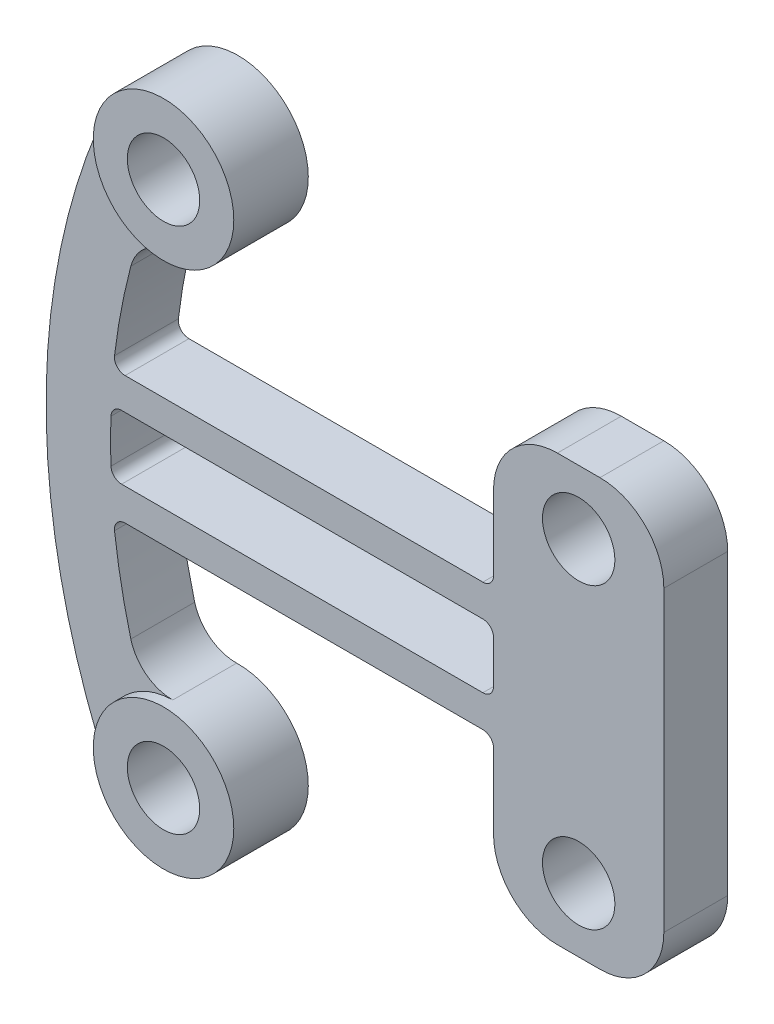
SolidWorks part; units mm, degrees
ref_plane "Front Plane" through (0, 0, 0) normal (0, 0, 1) x (1, 0, 0)
ref_plane "Top Plane" through (0, 0, 0) normal (0, 1, 0) x (1, 0, 0)
ref_plane "Right Plane" through (0, 0, 0) normal (1, 0, 0) x (0, 0, -1)
ref_plane "Plane1" through (0, 0, 0) normal (0, 0, -1) x (-1, 0, 0)
sketch "Sketch1" plane through (0, 0, 0) normal (0, 0, -1) x (-1, 0, 0)
  line L0 (-16, 3) -> (-16, -3)
  line L1 (-16, -3) -> (9.8641, -3)
  line L2 (9.8641, 3) -> (-16, 3)
  arc A0 (9.8641, -3) -> (8.4873, -9.4291) centre (-19.8438, 0) cw
  arc A1 (8.4873, -9.4291) -> (9.997, -13.7566) centre (7, -12.375) ccw
  arc A2 (9.997, -13.7566) -> (9.997, 13.7566) centre (-19.8438, 0) ccw
  arc A3 (9.997, 13.7566) -> (8.4873, 9.4291) centre (7, 12.375) ccw
  arc A4 (8.4873, 9.4291) -> (9.8641, 3) centre (-19.8438, 0) cw
extrude "Boss-Extrude1" add sketch "Sketch1" against normal blind 3
sketch "Sketch2" plane through (0, -3, 0) normal (0, -1, 0) x (1, 0, 0)
  line L0 (8, 3) -> (16, 3)
  line L1 (16, 3) -> (16, 0)
  line L2 (16, 0) -> (8, 0)
  line L3 (8, 0) -> (8, 3)
extrude "Boss-Extrude2" add sketch "Sketch2" along normal blind 7
sketch "Sketch3" plane through (0, 3, 0) normal (0, 1, 0) x (-1, 0, 0)
  line L0 (-16, 3) -> (-8, 3)
  line L1 (-8, 3) -> (-8, 0)
  line L2 (-8, 0) -> (-16, 0)
  line L3 (-16, 0) -> (-16, 3)
extrude "Boss-Extrude3" add sketch "Sketch3" along normal blind 7
sketch "Sketch4" plane through (0, 0, 3) normal (0, 0, 1) x (1, 0, 0)
  circle A0 centre (-7, 12.375) radius 3.3001
extrude "Boss-Extrude4" add sketch "Sketch4" along normal blind 0.5
sketch "Sketch5" plane through (0, 0, 3) normal (0, 0, 1) x (1, 0, 0)
  circle A0 centre (-7, -12.375) radius 3.3001
extrude "Boss-Extrude5" add sketch "Sketch5" along normal blind 0.5
sketch "Sketch6" plane through (0, 0, 3) normal (0, 0, 1) x (1, 0, 0)
  line L0 (8, 1.5) -> (-9.9482, 1.5)
  line L1 (-9.9482, -1.5) -> (8, -1.5)
  line L2 (8, -1.5) -> (8, 1.5)
  line L3 (8, -3) -> (-9.8641, -3) construction
  arc A0 (-9.9482, 1.5) -> (-9.9482, -1.5) centre (19.8732, 0) ccw
  dimension "D1" = 3
  dimension "D2" = 17.9482
  dimension "D3" = 1.5
extrude "Cut-Extrude1" cut sketch "Sketch6" against normal through all
hole_wizard "M3 Clearance Hole2" positions "Sketch8" profile "Sketch7" hole size "M3" standard "ANSI Metric" end condition through all
sketch "Sketch8" plane through (0, 0, 0) normal (0, 0, -1) x (-1, 0, 0)
  line L0 (-16, 10) -> (-8, 10) construction
  line L1 (-8, -10) -> (-16, -10) construction
  point P0 (-12, -7)
  point P1 (-12, 7)
  dimension "D1" = 3
  dimension "D2" = 3
sketch "Sketch7" plane through (12, -7, 0) normal (1, 0, 0) x (0, 1, 0)
  line L0 (0, 0) -> (0, 3.5)
  line L1 (0, 3.5) -> (1.7, 3.5)
  line L2 (1.7, 3.5) -> (1.7, 0)
  line L5 (1.7, 0) -> (0, 0)
  line L11 (0, -6.35) -> (0, 107.95) construction
  dimension "Thru Hole Dia." = 3.4
  dimension "Thru Hole Depth" = 3.5
hole_wizard "M3 Clearance Hole1" positions "Sketch10" profile "Sketch9" hole size "M3" standard "ANSI Metric" end condition through all
sketch "Sketch10" plane through (0, 0, 0) normal (0, 0, -1) x (-1, 0, 0)
  point P0 (7, 12.375)
  point P1 (7, -12.375)
sketch "Sketch9" plane through (-7, 12.375, 0) normal (1, 0, 0) x (0, 1, 0)
  line L0 (0, 0) -> (0, 3.5)
  line L1 (0, 3.5) -> (1.7, 3.5)
  line L2 (1.7, 3.5) -> (1.7, 0)
  line L5 (1.7, 0) -> (0, 0)
  line L11 (0, -6.35) -> (0, 107.95) construction
  dimension "Thru Hole Dia." = 3.4
  dimension "Thru Hole Depth" = 3.5
fillet "Fillet1" radius 0.5 8 edges at (8, 3, 1.5) (8, -3, 1.5) (-9.8641, 3, 1.5) (-9.9482, -1.5, 1.5) (8, 1.5, 1.5) (-9.9482, 1.5, 1.5) (-9.8641, -3, 1.5) (8, -1.5, 1.5) tangent propagation no
fillet "Fillet2" radius 2 2 edges at (-8.4873, -9.4291, 1.5) (-8.4873, 9.4291, 1.5) tangent propagation no
fillet "Fillet3" radius 3 4 edges at (16, -10, 1.5) (8, -10, 1.5) (16, 10, 1.5) (8, 10, 1.5) tangent propagation no
